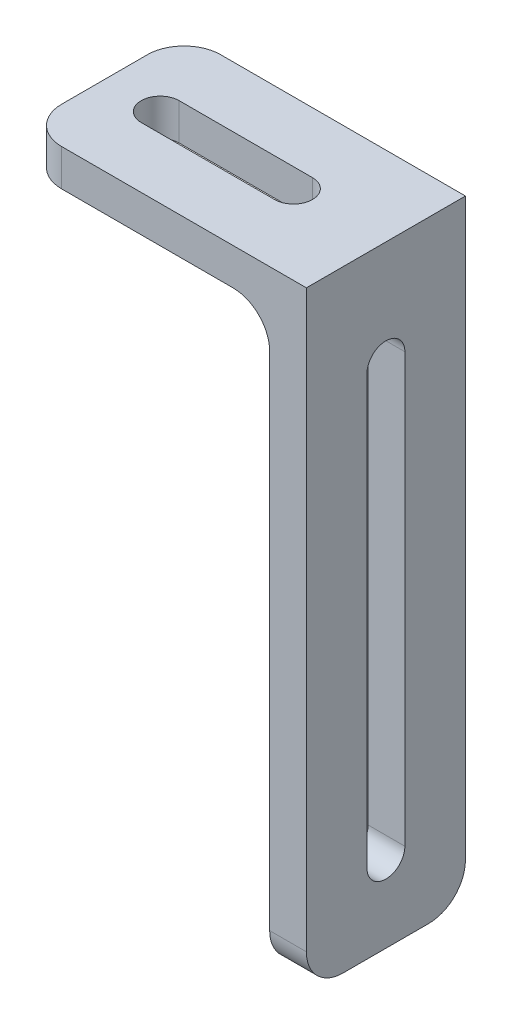
SolidWorks part; units mm, degrees
ref_plane "Front Plane" through (0, 0, 0) normal (0, 0, 1) x (1, 0, 0)
ref_plane "Top Plane" through (0, 0, 0) normal (0, 1, 0) x (1, 0, 0)
ref_plane "Right Plane" through (0, 0, 0) normal (1, 0, 0) x (0, 0, -1)
sketch "Sketch1" plane through (0, 0, 0) normal (0, 0, 1) x (1, 0, 0)
  line L0 (0, 0) -> (3, 0)
  line L1 (3, 0) -> (3, 50)
  line L2 (3, 50) -> (-20, 50)
  line L3 (-20, 50) -> (-20, 47)
  line L4 (-20, 47) -> (0, 47)
  line L5 (0, 47) -> (0, 0)
  dimension "D1" = 20
  dimension "D2" = 50
  dimension "D3" = 3
  dimension "D4" = 3
extrude "Boss-Extrude1" add sketch "Sketch1" along normal blind 13
sketch "Sketch6" plane through (3, 0, 0) normal (1, 0, 0) x (0, 0, -1)
  line L0 (-6.5, 50) -> (-6.5, 0) construction
  line L1 (-13, 50) -> (0, 50) construction
  line L2 (-13, 0) -> (0, 0) construction
  line L3 (-6.5, 41.45) -> (-6.5, 6.45) construction
  line L4 (-4.95, 41.45) -> (-4.95, 6.45)
  line L5 (-8.05, 41.45) -> (-8.05, 6.45)
  arc A0 (-4.95, 41.45) -> (-8.05, 41.45) centre (-6.5, 41.45) ccw
  arc A1 (-8.05, 6.45) -> (-4.95, 6.45) centre (-6.5, 6.45) ccw
  point P8 (-6.5, 23.95)
  point P13 (-6.5, 43)
  dimension "D1" = 3.1
  dimension "D2" = 7
  dimension "D3" = 35
extrude "Cut-Extrude1" cut sketch "Sketch6" against normal through all
sketch "Sketch7" plane through (0, 50, 0) normal (0, 1, 0) x (1, 0, 0)
  line L0 (-20, -6.5) -> (3, -6.5) construction
  line L1 (-20, -13) -> (-20, 0) construction
  line L2 (3, -13) -> (3, 0) construction
  line L3 (-15.45, -6.5) -> (-4.55, -6.5) construction
  line L4 (-15.45, -4.95) -> (-4.55, -4.95)
  line L5 (-15.45, -8.05) -> (-4.55, -8.05)
  arc A0 (-15.45, -4.95) -> (-15.45, -8.05) centre (-15.45, -6.5) ccw
  arc A1 (-4.55, -8.05) -> (-4.55, -4.95) centre (-4.55, -6.5) ccw
  point P8 (-10, -6.5)
  point P13 (-17, -6.5)
  point P14 (-3, -6.5)
  dimension "D2" = 6
  dimension "D1" = 3
  dimension "D3" = 3.1
extrude "Cut-Extrude2" cut sketch "Sketch7" against normal through all contours L4 A1 L5 A0
fillet "Fillet1" radius 3 1 edges at (0, 47, 6.5)
fillet "Fillet2" radius 3 4 edges at (1.5, 0, 0) (1.5, 0, 13) (-20, 48.5, 13) (-20, 48.5, 0)
